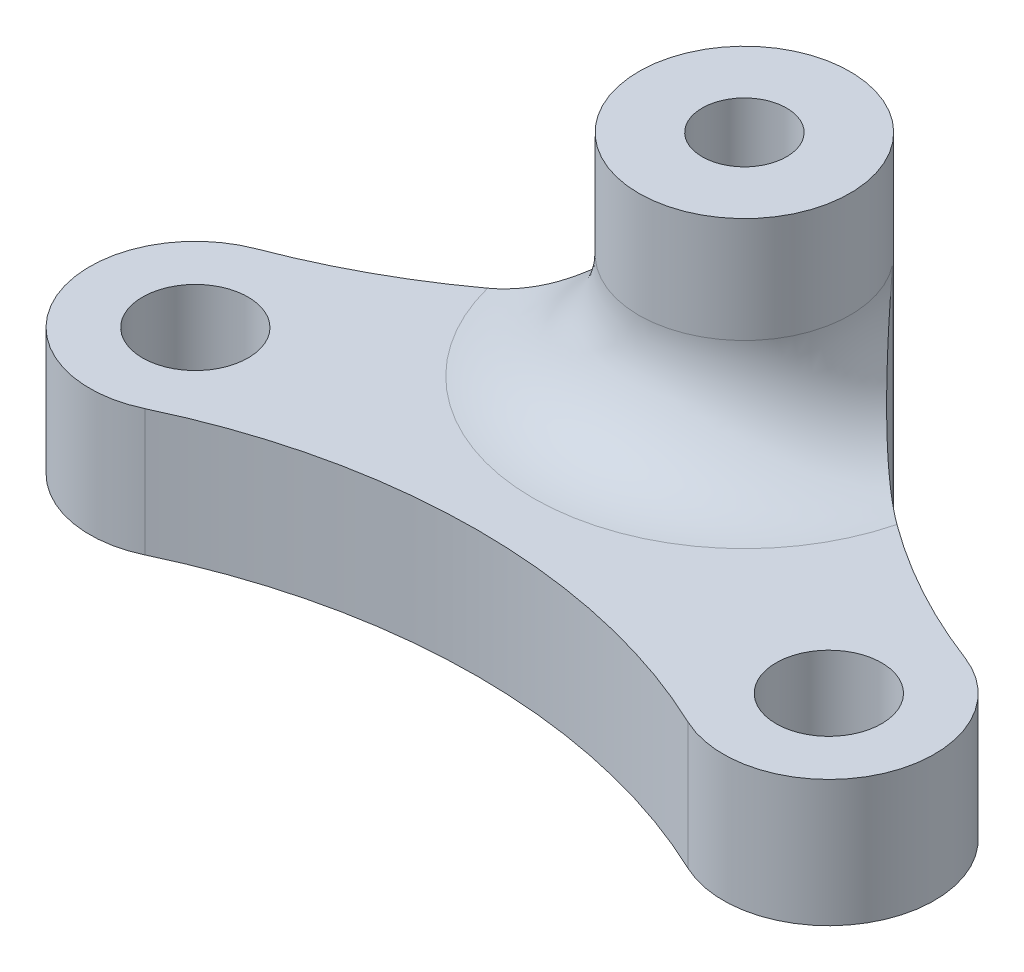
SolidWorks part; units mm, degrees
ref_plane "Спереди" through (0, 0, 0) normal (0, 0, 1) x (1, 0, 0)
ref_plane "Сверху" through (0, 0, 0) normal (0, 1, 0) x (1, 0, 0)
ref_plane "Справа" through (0, 0, 0) normal (1, 0, 0) x (0, 0, -1)
sketch "Эскиз1" plane through (0, 0, 0) normal (0, 1, 0) x (1, 0, 0)
  line L0 (0, -1000) -> (0, 49000) construction
  line L1 (-1000, -11) -> (49000, -11) construction
  circle A0 centre (0, 0) radius 2
  circle A1 centre (-15, -11) radius 2.5
  circle A2 centre (-15, -11) radius 5
  circle A3 centre (0, 0) radius 5
  circle A4 centre (15, -11) radius 2.5
  circle A5 centre (15, -11) radius 5
  arc A6 (-12.8571, -15.5175) -> (12.8571, -15.5175) centre (0, -42.6228) cw
  arc A7 (-16.7791, -6.3272) -> (-3.9219, 3.1013) centre (-27.4536, 21.7094) ccw
  arc A8 (16.7791, -6.3272) -> (3.9219, 3.1013) centre (27.4536, 21.7094) cw
  dimension "D1" = 4
  dimension "D3" = 5
  dimension "D4" = 10
  dimension "D5" = 10
  dimension "D7" = 30
  dimension "D8" = 30
  dimension "D2" = 11
  dimension "D6" = 15
extrude "Бобышка-Вытянуть1" add sketch "Эскиз1" along normal blind 6 contours A5 A8 A3 A7 A2 A6 | A3 A0 | A5 A4 | A2 A1 region at (-10.8938, 0, 13.597) region at (0, 0, 7.4104) region at (0, 0, -4.8586) region at (10.5313, 0, 9.093)
sketch "Эскиз2" plane through (0, 6, 0) normal (0, 1, 0) x (1, 0, 0)
  circle A0 centre (0, 0) radius 5
  arc A1 (3.9219, 3.1013) -> (-3.9219, 3.1013) centre (0, 0) ccw construction
  circle A2 centre (0, 0) radius 2 construction
  circle A3 centre (0, 0) radius 2
extrude "Бобышка-Вытянуть2" add sketch "Эскиз2" along normal blind 10
fillet "Скругление1" radius 5 1 edges at (0, 6, 5)
